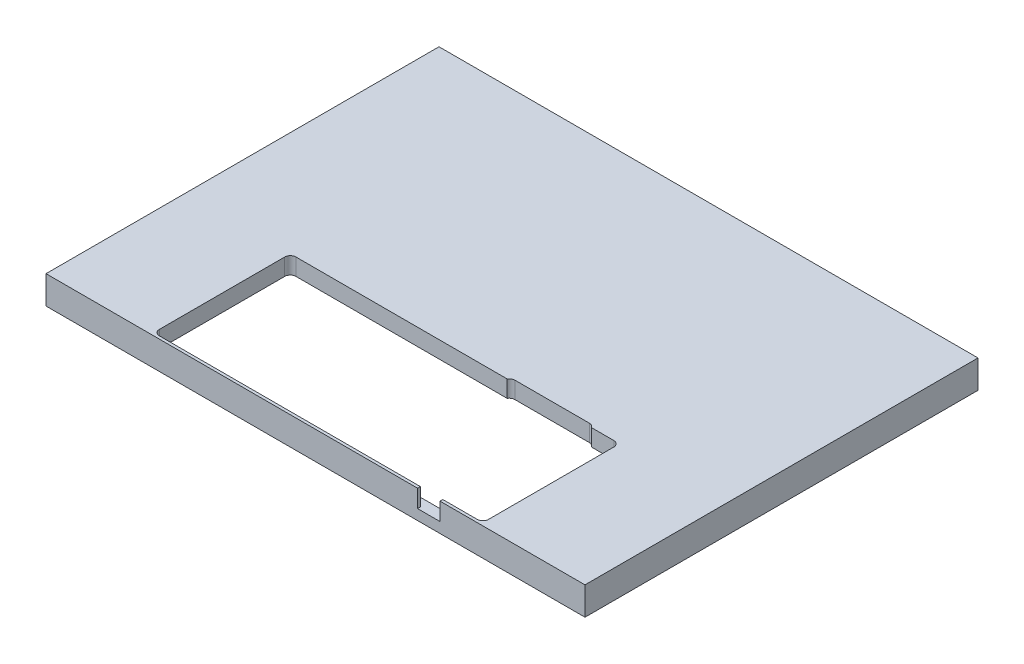
SolidWorks part; units mm, degrees
ref_plane "Front Plane" through (0, 0, 0) normal (0, 0, 1) x (1, 0, 0)
ref_plane "Top Plane" through (0, 0, 0) normal (0, 1, 0) x (1, 0, 0)
ref_plane "Right Plane" through (0, 0, 0) normal (1, 0, 0) x (0, 0, -1)
sketch "Sketch1" plane through (0, 0, 0) normal (0, 1, 0) x (1, 0, 0)
  line L0 (5.08, 5.08) -> (238.76, 5.08)
  line L1 (0, 0) -> (243.84, 0)
  line L2 (0, 0) -> (0, 177.8)
  line L3 (0, 177.8) -> (243.84, 177.8)
  line L4 (243.84, 0) -> (243.84, 177.8)
  line L5 (238.76, 5.08) -> (238.76, 172.72)
  line L6 (5.08, 172.72) -> (238.76, 172.72)
  line L7 (5.08, 5.08) -> (5.08, 172.72)
  dimension "D1" = 177.8
  dimension "D2" = 243.84
  dimension "D3" = 5.08
extrude "Boss-Extrude7" add sketch "Sketch1" along normal blind 12.7
sketch "Sketch6" plane through (0, 12.7, 0) normal (0, 1, 0) x (1, 0, 0)
  line L0 (5.08, 172.72) -> (5.08, 5.08)
  line L1 (5.08, 5.08) -> (238.76, 5.08)
  line L2 (238.76, 5.08) -> (238.76, 172.72)
  line L3 (238.76, 172.72) -> (5.08, 172.72)
extrude "Boss-Extrude8" add sketch "Sketch6" against normal blind 7.62
sketch "Sketch7" plane through (0, 12.7, 0) normal (0, 1, 0) x (1, 0, 0)
  line L0 (0, 0) -> (243.84, 0) construction
  line L1 (0, 177.8) -> (0, 0) construction
  line L2 (243.84, 0) -> (243.84, 177.8) construction
  line L3 (196.37, 1.27) -> (178.2581, 1.27)
  line L4 (47.47, 1.27) -> (47.47, 63.07)
  line L6 (196.37, 63.07) -> (196.37, 1.27)
  line L8 (47.47, 32.17) -> (0, 32.17) construction
  line L9 (196.37, 32.17) -> (243.84, 32.17) construction
  line L11 (168.0981, 0) -> (178.2581, 0)
  line L12 (178.2581, 0) -> (178.2581, 1.27)
  line L14 (157.9954, 1.27) -> (47.47, 1.27)
  line L15 (157.9954, 1.27) -> (168.0981, 1.27)
  line L16 (168.0981, 1.27) -> (168.0981, 0)
  line L18 (183.67, 64.34) -> (145.57, 64.34)
  line L20 (196.37, 63.07) -> (183.67, 63.07)
  line L21 (145.57, 63.07) -> (47.47, 63.07)
  line L22 (183.67, 63.07) -> (183.67, 64.34)
  line L23 (145.57, 63.07) -> (145.57, 64.34)
  dimension "D1" = 1.27
  dimension "D2" = 148.9
  dimension "D3" = 61.8
  dimension "D4" = 10.16
  dimension "D5" = 38.1
  dimension "D6" = 12.7
  dimension "D7" = 1.27
extrude "Cut-Extrude2" cut sketch "Sketch7" against normal blind 8 contours L4 L21 L23 L18 L22 L20 L6 L3 L12 L11 L16 L15 L14
fillet "Fillet1" radius 2.54 4 edges at (47.47, 8.89, -63.07) (47.47, 8.7, -1.27) (196.37, 8.7, -1.27) (196.37, 8.89, -63.07)
fillet "Fillet2" radius 2.54 2 edges at (145.57, 8.89, -64.34) (183.67, 8.89, -64.34)
sketch "Sketch8" plane through (0, 12.7, 0) normal (0, 1, 0) x (1, 0, 0)
  line L0 (50.7746, 99.4151) -> (50.7746, 110.8197)
  line L1 (50.7746, 110.8197) -> (62.7634, 110.8197)
  line L2 (62.7634, 110.8197) -> (62.7634, 99.4151)
  line L3 (62.7634, 99.4151) -> (50.7746, 99.4151)
  line L4 (77.2414, 99.4151) -> (65.2526, 99.4151)
  line L5 (65.2526, 99.4151) -> (65.2526, 110.8197)
  line L6 (65.2526, 110.8197) -> (77.2414, 110.8197)
  line L7 (77.2414, 110.8197) -> (77.2414, 99.4151)
  line L8 (91.7194, 99.4151) -> (79.7306, 99.4151)
  line L9 (79.7306, 99.4151) -> (79.7306, 110.8197)
  line L10 (79.7306, 110.8197) -> (91.7194, 110.8197)
  line L11 (91.7194, 110.8197) -> (91.7194, 99.4151)
  line L12 (106.1974, 99.4151) -> (94.2086, 99.4151)
  line L13 (94.2086, 99.4151) -> (94.2086, 110.8197)
  line L14 (94.2086, 110.8197) -> (106.1974, 110.8197)
  line L15 (106.1974, 110.8197) -> (106.1974, 99.4151)
  line L16 (120.6754, 99.4151) -> (108.6866, 99.4151)
  line L17 (108.6866, 99.4151) -> (108.6866, 110.8197)
  line L18 (108.6866, 110.8197) -> (120.6754, 110.8197)
  line L19 (120.6754, 110.8197) -> (120.6754, 99.4151)
  line L20 (135.1534, 99.4151) -> (123.1646, 99.4151)
  line L21 (123.1646, 99.4151) -> (123.1646, 110.8197)
  line L22 (123.1646, 110.8197) -> (135.1534, 110.8197)
  line L23 (135.1534, 110.8197) -> (135.1534, 99.4151)
  line L24 (149.6314, 99.4151) -> (137.6426, 99.4151)
  line L25 (137.6426, 99.4151) -> (137.6426, 110.8197)
  line L26 (137.6426, 110.8197) -> (149.6314, 110.8197)
  line L27 (149.6314, 110.8197) -> (149.6314, 99.4151)
  line L28 (164.1094, 99.4151) -> (152.1206, 99.4151)
  line L29 (152.1206, 99.4151) -> (152.1206, 110.8197)
  line L30 (152.1206, 110.8197) -> (164.1094, 110.8197)
  line L31 (164.1094, 110.8197) -> (164.1094, 99.4151)
  line L32 (178.5874, 99.4151) -> (166.5986, 99.4151)
  line L33 (166.5986, 99.4151) -> (166.5986, 110.8197)
  line L34 (166.5986, 110.8197) -> (178.5874, 110.8197)
  line L35 (178.5874, 110.8197) -> (178.5874, 99.4151)
  line L36 (193.0654, 99.4151) -> (181.0766, 99.4151)
  line L37 (181.0766, 99.4151) -> (181.0766, 110.8197)
  line L38 (181.0766, 110.8197) -> (193.0654, 110.8197)
  line L39 (193.0654, 110.8197) -> (193.0654, 99.4151)
  line L40 (120.6754, 105.1174) -> (123.1646, 105.1174) construction
  line L41 (123.1646, 105.1174) -> (243.84, 105.1174) construction
  line L42 (243.84, 0) -> (243.84, 177.8) construction
  line L43 (120.6754, 105.1174) -> (0, 105.1174) construction
  line L44 (0, 177.8) -> (0, 0) construction
  line L45 (48.2346, 99.4151) -> (22.8346, 99.4151)
  line L46 (22.8346, 99.4151) -> (22.8346, 110.8197)
  line L47 (22.8346, 110.8197) -> (48.2346, 110.8197)
  line L48 (48.2346, 110.8197) -> (48.2346, 99.4151)
  line L53 (217.7065, 105.1174) -> (217.7065, 110.8265) construction
  line L54 (217.7065, 105.1174) -> (217.7065, 99.4082) construction
  line L55 (195.6054, 110.8197) -> (195.6054, 99.4151)
  line L56 (195.6054, 99.4151) -> (233.7054, 99.4151)
  line L57 (233.7054, 99.4151) -> (233.7054, 110.8265)
  line L58 (233.7054, 110.8265) -> (195.6054, 110.8197)
  line L59 (193.0654, 99.4151) -> (195.6054, 99.4151) construction
  line L60 (193.0654, 110.8197) -> (195.6054, 110.8197) construction
  line L61 (74.3652, 71.3242) -> (74.3652, 82.7542)
  line L62 (74.3652, 82.7542) -> (169.6152, 82.7542)
  line L63 (169.6152, 82.7542) -> (169.6152, 71.3242)
  line L64 (169.6152, 71.3242) -> (74.3652, 71.3242)
  line L65 (71.8252, 71.3242) -> (71.8252, 82.7542)
  line L66 (71.8252, 82.7542) -> (52.7752, 82.7542)
  line L67 (52.7752, 82.7542) -> (52.7752, 71.3242)
  line L68 (52.7752, 71.3242) -> (71.8252, 71.3242)
  line L69 (48.6612, 71.3242) -> (48.6612, 82.7542)
  line L70 (48.6612, 82.7542) -> (40.2886, 82.7542)
  line L71 (40.2886, 82.7542) -> (40.2886, 71.3242)
  line L72 (40.2886, 71.3242) -> (48.6612, 71.3242)
  dimension "D1" = 11.9888
  dimension "D2" = 11.4046
  dimension "D4" = 25.4
  dimension "D5" = 2.4892
  dimension "D6" = 2.54
  dimension "D7" = 38.1
  dimension "D8" = 2.54
  dimension "D9" = 95.25
  dimension "D10" = 11.43
  dimension "D11" = 11.43
  dimension "D12" = 2.54
  dimension "D13" = 19.05
  dimension "D14" = 8.3726
  dimension "D3" = 10
